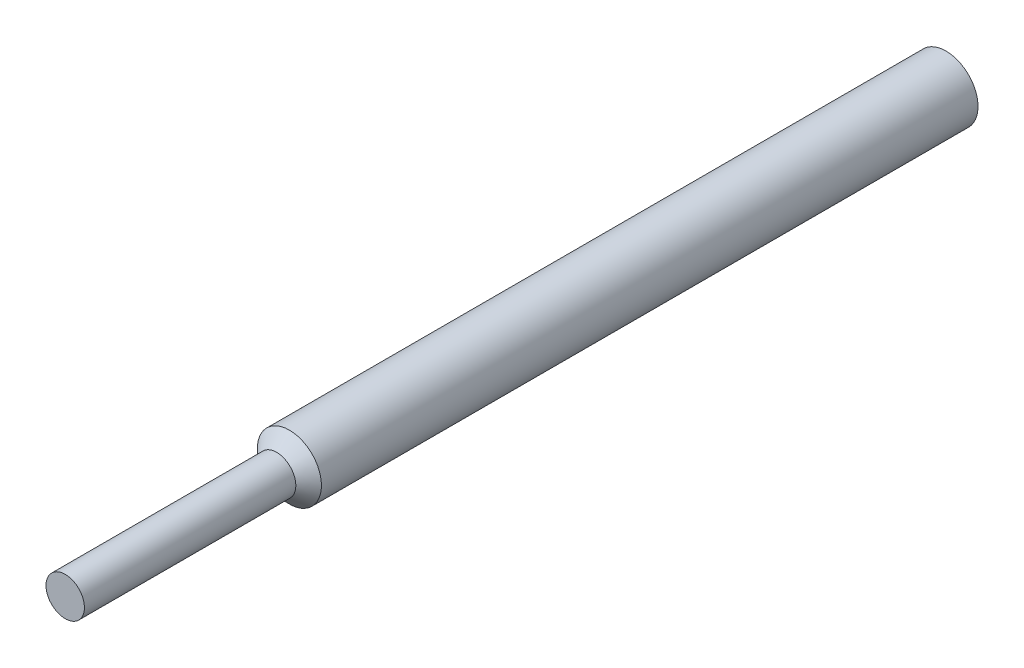
SolidWorks part; units mm, degrees
ref_plane "Front Plane" through (0, 0, 0) normal (0, 0, 1) x (1, 0, 0)
ref_plane "Top Plane" through (0, 0, 0) normal (0, 1, 0) x (1, 0, 0)
ref_plane "Right Plane" through (0, 0, 0) normal (1, 0, 0) x (0, 0, -1)
sketch "Sketch1" plane through (0, 0, 0) normal (1, 0, 0) x (0, 0, -1)
  line L0 (0, 0) -> (0, 6)
  line L1 (0, 6) -> (66, 6)
  line L2 (66, 6) -> (66, 10)
  line L3 (66, 10) -> (275, 10)
  line L4 (275, 10) -> (275, 0)
  line L5 (275, 0) -> (0, 0)
  dimension "D1" = 66
  dimension "D2" = 275
  dimension "D3" = 10
  dimension "D4" = 6
revolve "Revolve1" add sketch "Sketch1" angle 360 about L5
chamfer "Chamfer1" distance 4 angle 45 1 edges at (0, 10, -66)
